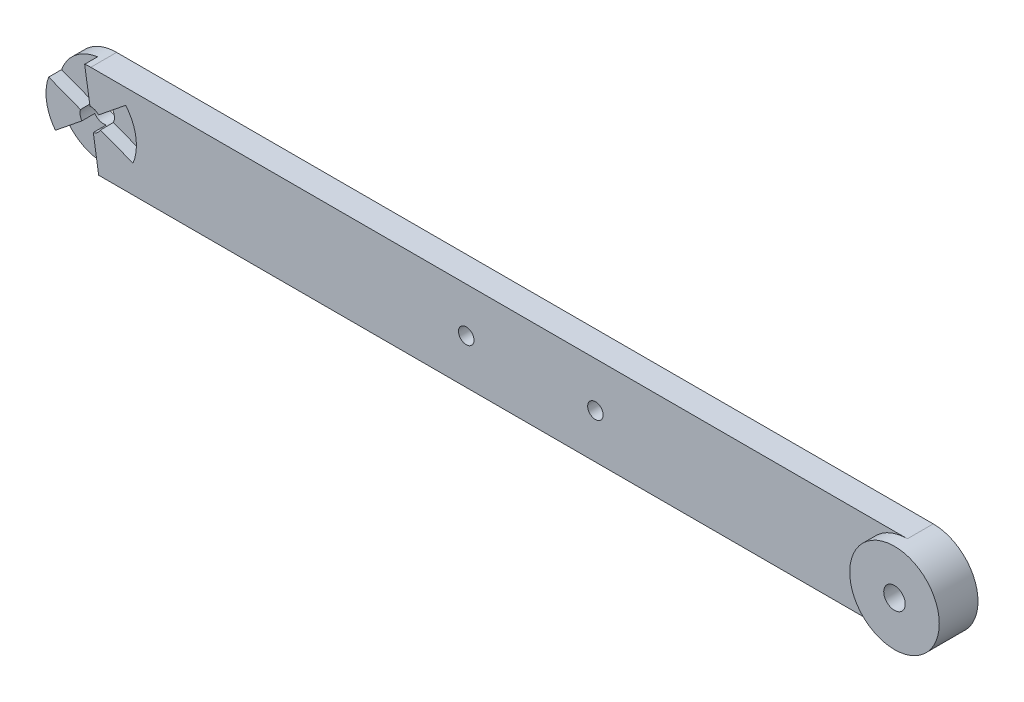
SolidWorks part; units mm, degrees
ref_plane "Front Plane" through (0, 0, 0) normal (0, 0, 1) x (1, 0, 0)
ref_plane "Top Plane" through (0, 0, 0) normal (0, 1, 0) x (1, 0, 0)
ref_plane "Right Plane" through (0, 0, 0) normal (1, 0, 0) x (0, 0, -1)
sketch "Sketch1" plane through (0, 0, 0) normal (0, 0, 1) x (1, 0, 0)
  line L0 (189.7, -10.4) -> (0, -10.4)
  line L1 (189.7, 10.4) -> (0, 10.4)
  circle A4 centre (0, 0) radius 2.5
  circle A5 centre (189.7, 0) radius 2.5
  arc A6 (0, 10.4) -> (0, -10.4) centre (0, 0) ccw
  arc A7 (189.7, -10.4) -> (189.7, 10.4) centre (189.7, 0) ccw
  arc A9 (0, -10.4) -> (0, 10.4) centre (0, 0) ccw construction
  circle A10 centre (0, 0) radius 10.4 construction
  arc A11 (189.7, 10.4) -> (189.7, -10.4) centre (189.7, 0) ccw construction
  circle A12 centre (189.7, 0) radius 10.4 construction
  circle A13 centre (189.7, 0) radius 1.4996 construction
  circle A15 centre (0, 0) radius 2.4001
  point P11 (170.2346, 97.4995)
  point P18 (75.4, 97.5)
  dimension "D1" = 5
  dimension "D3" = 1.0004
  dimension "D4" = 4.8001
  dimension "D2" = 10.4
  dimension "D5" = 189.7
extrude "Boss-Extrude1" add sketch "Sketch1" along normal blind 6 contours L0 A7 L1 A6 A4 A5 region at (94.85, 0, 0)
sketch "Sketch6" plane through (0, 0, 0) normal (0, 0, -1) x (-1, 0, 0)
  line L0 (0, 0) -> (6.6622, 8.2447) construction
  line L1 (0, 0) -> (-10.4, 0) construction
  line L2 (0, 0) -> (9.892, 3.8091) construction
  line L3 (0, 0) -> (1.6472, 10.4712) construction
  line L4 (2.3974, 0.7088) -> (9.9638, 3.6224)
  line L5 (0.1897, 2.4928) -> (1.4497, 10.5023)
  line L6 (-0.5848, -2.4306) -> (-1.8448, -10.4401)
  line L7 (0.0719, -0.1866) -> (9.9638, 3.6224) construction
  line L8 (-0.1976, 0.0311) -> (1.4497, 10.5023) construction
  line L9 (2.064, -1.4107) -> (8.3704, -6.5066)
  line L10 (0.1257, 0.1556) -> (8.3704, -6.5066) [skipped]
  line L11 (-0.1976, 0.0311) -> (-1.8448, -10.4401) [skipped]
  line L12 (0.0719, -0.1866) -> (-9.8201, -3.9957) [skipped]
  line L13 (0.1257, 0.1556) -> (-8.119, 6.8177) [skipped]
  line L14 (-1.8126, 1.7218) -> (-8.119, 6.8177)
  line L15 (-2.2537, -1.0821) -> (-9.8201, -3.9957)
  circle A0 centre (0, 0) radius 10.4 construction
  arc A1 (0, -10.4) -> (0, 10.4) centre (0, 0) ccw construction
  arc A2 (9.9621, 3.6217) -> (1.4494, 10.5004) centre (0, 0) ccw
  arc A3 (9.9621, 3.6217) -> (1.4494, 10.5004) centre (0, 0) ccw
  arc A4 (9.9621, 3.6217) -> (1.4494, 10.5004) centre (0, 0) ccw
  circle A5 centre (0, 0) radius 2.5 construction
  arc A6 (2.3974, 0.7088) -> (0.1897, 2.4928) centre (0, 0) ccw
  arc A7 (-0.5848, -2.4306) -> (2.064, -1.4107) centre (0, 0) ccw
  circle A8 centre (0, 0) radius 10.6 construction
  arc A9 (-1.8445, -10.4383) -> (8.369, -6.5054) centre (0, 0) ccw
  arc A10 (-1.8126, 1.7218) -> (-2.2537, -1.0821) centre (0, 0) ccw
  arc A11 (-8.1176, 6.8165) -> (-9.8183, -3.995) centre (0, 0) ccw
  point P8 (-0.7033, -1.0005)
  point P13 (7.6704, -5.9409)
  point P14 (0.0719, -0.1866)
  point P15 (9.124, 3.299)
  point P22 (10.1368, 3.0991)
  point P27 (0, 0)
  point P34 (0, 0)
  point P51 (0, 0)
  dimension "D3" = 60
  dimension "D2" = 128.94
  dimension "D4" = 30
  dimension "D6" = 0.2
  dimension "D8" = 3
  dimension "D1" = 0.2
  dimension "D5" = 0.2
  dimension "D7" = 3
extrude "Cut-Extrude3" cut sketch "Sketch6" against normal blind 3 contours L5 L4 | L9 L6 | L14 A11 L15 region at (-4.3826, 5.4237, 0) region at (-2.5057, -6.5073, 0) region at (6.8883, 1.0836, 0)
sketch "Sketch4" plane through (0, 0, 0) normal (0, 0, -1) x (-1, 0, 0)
  arc A0 (-189.7, 10.4) -> (-189.7, -10.4) centre (-189.7, 0) ccw construction
  arc A1 (-189.7, 10.4) -> (-189.7, -10.4) centre (-189.7, 0) ccw
  arc A2 (-189.7, 10.4) -> (-189.7, -10.4) centre (-189.7, 0) cw
  circle A3 centre (-189.7, 0) radius 2.5 construction
  circle A4 centre (-189.7, 0) radius 2.5
extrude "Boss-Extrude2" add sketch "Sketch4" along normal blind 3
mirror "Mirror1" about plane through (0, 0, 0) normal (0, 0, 1) of bodies 103
sketch "Sketch7" plane through (0, 0, -6) normal (0, 0, -1) x (-1, 0, 0)
  point P0 (-117.2241, -0.0523)
  point P3 (-87.2242, 0)
delete or keep bodies "Body-Delete/Keep 1" type delete bodies bodies 103
hole_wizard "M3 Clearance Hole1" positions "Sketch7" profile "Sketch8" hole size "M3" standard "ANSI Metric" end condition through all
sketch "Sketch8" plane through (117.2241, -0.0523, -6) normal (1, 0, 0) x (0, 1, 0)
  line L0 (0, 0) -> (0, 9)
  line L1 (0, 9) -> (1.8, 9)
  line L2 (1.8, 9) -> (1.8, 0)
  line L5 (1.8, 0) -> (0, 0)
  line L11 (0, -6.35) -> (0, 107.95) construction
  dimension "Thru Hole Dia." = 3.6
  dimension "Thru Hole Depth" = 9
